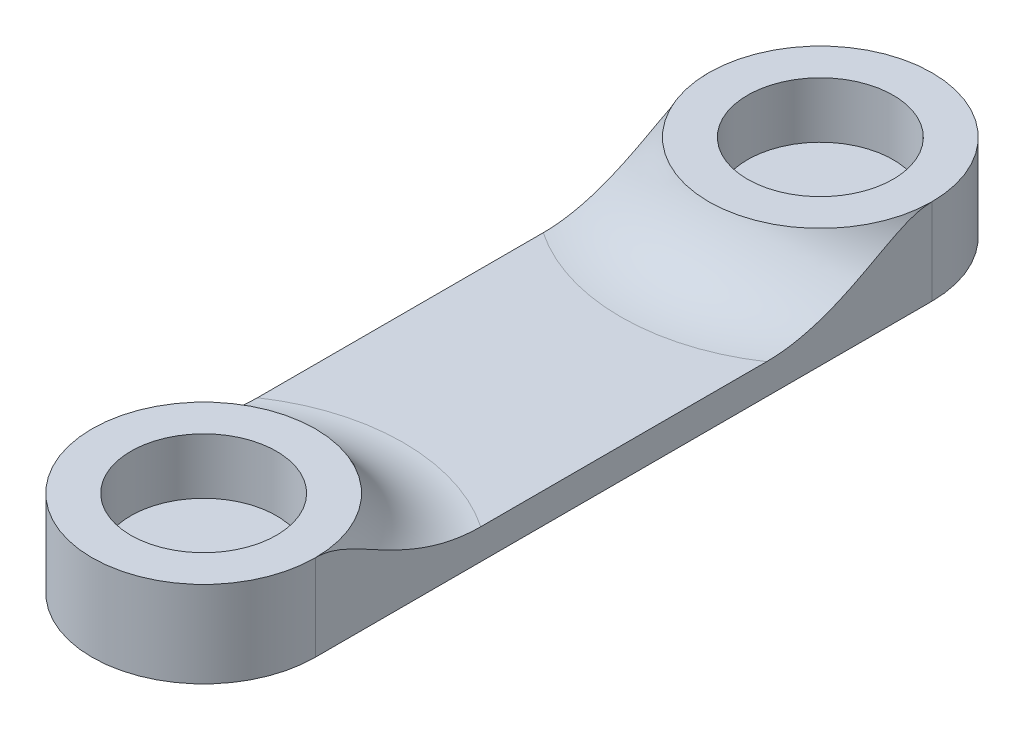
SolidWorks part; units mm, degrees
ref_plane "Plano frontal" through (0, 0, 0) normal (0, 0, 1) x (1, 0, 0)
ref_plane "Plano superior" through (0, 0, 0) normal (0, 1, 0) x (1, 0, 0)
ref_plane "Plano direito" through (0, 0, 0) normal (1, 0, 0) x (0, 0, -1)
sketch "Esboço1" plane through (0, 0, 0) normal (0, 1, 0) x (1, 0, 0)
  line L0 (0, 744.0149) -> (0, -296.7841) construction
  line L3 (-11.5, -69.8378) -> (-11.5, -133.3378)
  line L4 (11.5, -69.8378) -> (11.5, -133.3378)
  circle A2 centre (0, -69.8378) radius 11.5
  circle A3 centre (0, -133.3378) radius 11.5
  circle A4 centre (0, -69.8378) radius 7.5
  circle A5 centre (0, -133.3378) radius 7.5
  dimension "D1" = 63.5
  dimension "D2" = 23
  dimension "D3" = 23
  dimension "D4" = 15
  dimension "D5" = 15
extrude "Ressalto-extrusão1" add sketch "Esboço1" along normal blind 3.125 contours L0 A2 L3 A3 | L0 A3 A5 | L0 A5 | A5 L0 | A3 L0 A5 | A2 L0 A3 L4 | A2 region at (6.0956, 0, 101.5878) region at (-6.0956, 0, 101.5878) region at (7.9499, 0, 141.2877) region at (-7.9499, 0, 125.3879) region at (3.1831, 0, 133.3378) region at (-3.1831, 0, 133.3378)
extrude "Ressalto-extrusão2" add sketch "Esboço1<3>" along normal blind 5.75 from surface contours L0 A2 A4 | A2 L0 A4 | L0 A3 A5 | A3 L0 A5 region at (7.9499, 0, 61.8879) region at (-0.2571, 0, 60.3378) region at (7.9499, 0, 141.2877) region at (-7.9499, 0, 125.3879) starting at face at (0, 3.125, 101.5878)
sketch "Esboço1<3>" plane through (0, 0, 0) normal (0, 1, 0) x (1, 0, 0) same geometry as "Esboço1"
fillet "Filete2" radius 10 2 edges at (0, 3.125, 121.8378) (0, 3.125, 81.3378)
